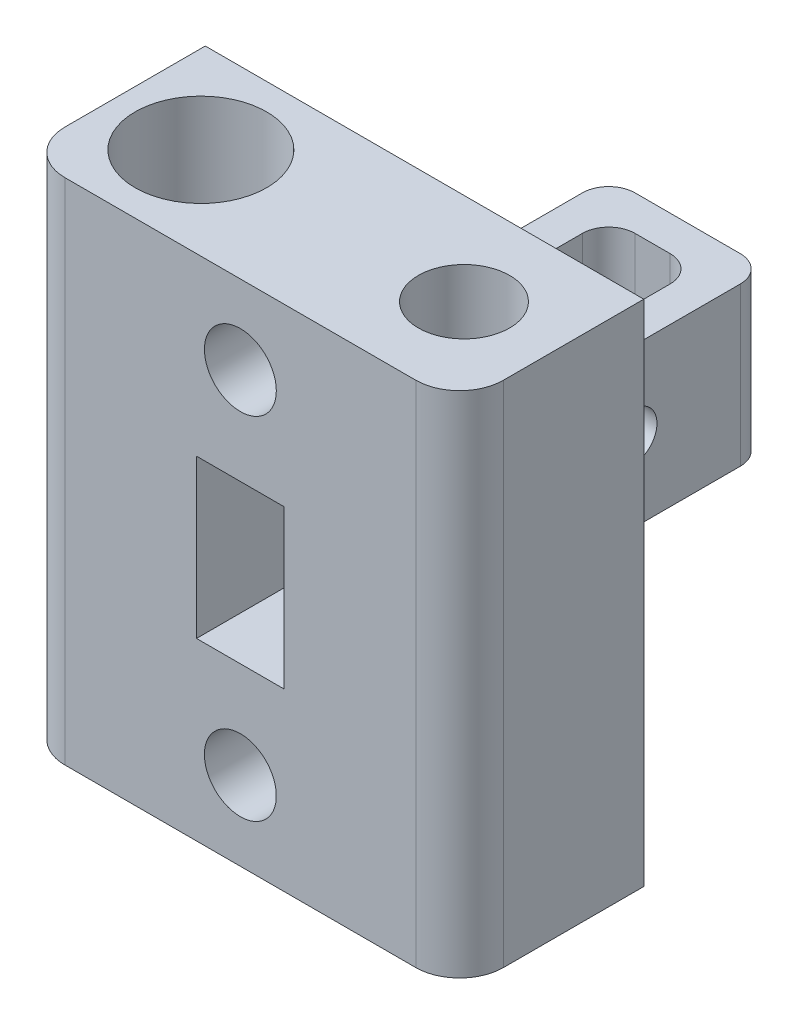
SolidWorks part; units mm, degrees
ref_plane "Front Plane" through (0, 0, 0) normal (0, 0, 1) x (1, 0, 0)
ref_plane "Top Plane" through (0, 0, 0) normal (0, 1, 0) x (1, 0, 0)
ref_plane "Right Plane" through (0, 0, 0) normal (1, 0, 0) x (0, 0, -1)
sketch "Sketch1" plane through (0, 0, 0) normal (0, 1, 0) x (1, 0, 0)
  line L1 (-25, 10.5) -> (25, 10.5)
  line L2 (-25, 10.5) -> (-25, -10.5)
  line L3 (-25, -10.5) -> (25, -10.5)
  line L4 (25, 10.5) -> (25, -10.5)
  line L5 (-25, 10.5) -> (25, -10.5) construction
  line L6 (-25, -10.5) -> (25, 10.5) construction
  point P0 (0, 0)
  dimension "D1" = 21
  dimension "D2" = 50
extrude "Boss-Extrude1" add sketch "Sketch1" along normal blind 58
sketch "Sketch3" plane through (0, 58, 0) normal (0, 1, 0) x (1, 0, 0)
  line L0 (-15, 0) -> (15, 0) construction
  circle A0 centre (-15, 0) radius 7.5
  dimension "D1" = 15
  dimension "D2" = 30
extrude "Cut-Extrude1" cut sketch "Sketch3" against normal blind 24 contours A0
sketch "Sketch4" plane through (0, 58, 0) normal (0, 1, 0) x (1, 0, 0)
  line L0 (-15, 0) -> (15, 0) construction
  circle A0 centre (15, 0) radius 5.2
  dimension "D1" = 10.4
extrude "Cut-Extrude2" cut sketch "Sketch4" against normal up to next
sketch "Sketch5" plane through (0, 0, 0) normal (0, -1, 0) x (1, 0, 0)
  circle A1 centre (-15, 0) radius 7.5
  circle A2 centre (-15, 0) radius 7.5
  dimension "D1" = 0
extrude "Cut-Extrude3" cut sketch "Sketch5" against normal blind 24
sketch "Sketch6" plane through (0, 0, 0) normal (0, -1, 0) x (1, 0, 0)
  circle A0 centre (-15, 0) radius 4.5
extrude "Cut-Extrude4" cut sketch "Sketch6" against normal up to next
sketch "Sketch7" plane through (0, 0, 10.5) normal (0, 0, 1) x (1, 0, 0)
  line L0 (0, 58) -> (0, 0) construction
  line L1 (-25, 58) -> (25, 58) construction
  line L2 (-25, 0) -> (25, 0) construction
  line L3 (-25, 29) -> (25, 29) construction
  line L4 (-25, 58) -> (-25, 0) construction
  line L5 (25, 58) -> (25, 0) construction
  circle A1 centre (0, 49) radius 4.1
  circle A2 centre (0, 9) radius 4.1
  point P24 (0, 9)
  dimension "D1" = 8.2
  dimension "D2" = 9
sketch "Sketch8" plane through (0, 0, 10.5) normal (0, 0, 1) x (1, 0, 0)
  line L0 (-25, 29) -> (25, 29) construction
  line L1 (-25, 58) -> (-25, 0) construction
  line L2 (25, 58) -> (25, 0) construction
  line L3 (0, 58) -> (0, 0) construction
  line L4 (-25, 58) -> (25, 58) construction
  line L6 (-5, 20) -> (5, 20)
  line L7 (-5, 20) -> (-5, 38)
  line L8 (-5, 38) -> (5, 38)
  line L9 (5, 20) -> (5, 38)
  line L10 (-5, 20) -> (5, 38) construction
  line L11 (-5, 38) -> (5, 20) construction
  point P11 (0, 29)
  dimension "D1" = 18
  dimension "D2" = 10
extrude "Cut-Extrude5" cut sketch "Sketch8" against normal up to next
sketch "Sketch10" plane through (0, 0, -10.5) normal (0, 0, -1) x (-1, 0, 0)
  line L0 (-25, 29) -> (25, 29) construction
  line L1 (-25, 58) -> (-25, 0) construction
  line L2 (25, 58) -> (25, 0) construction
  line L3 (0, 58) -> (0, 0) construction
  line L4 (-25, 58) -> (25, 58) construction
extrude "Cut-Extrude6" cut sketch "Sketch7" against normal blind 15
sketch "Sketch11" plane through (0, 0, -10.5) normal (0, 0, -1) x (-1, 0, 0)
  line L0 (-25, 29) -> (25, 29) construction
  line L1 (9, 38) -> (5, 38)
  line L2 (9, 38) -> (9, 20)
  line L3 (9, 20) -> (5, 20)
  line L4 (5, 38) -> (5, 20)
  line L5 (9, 38) -> (5, 20) construction
  line L6 (9, 20) -> (5, 38) construction
  line L7 (0, 58) -> (0, 0) construction
  line L8 (0, 58) -> (0, 0)
  line L9 (-9, 20) -> (-5, 20)
  line L10 (-5, 38) -> (-5, 20)
  line L11 (-9, 38) -> (-5, 38)
  line L12 (-9, 38) -> (-9, 20)
  point P0 (7, 29)
  line M7 (-5, 20) -> (-5, 38)
  line M9 (5, 38) -> (5, 20)
  dimension "D1" = 5
  dimension "D2" = 4
  dimension "D3" = 18
extrude "Boss-Extrude2" add sketch "Sketch11" along normal blind 26 contours L1 L4 L3 L2 M9 | L11 L12 L9 L10 M7 region at (-7, 29, -10.5) region at (7, 29, -10.5)
sketch "Sketch12" plane through (0, 0, -36.5) normal (0, 0, -1) x (-1, 0, 0)
  line L1 (9, 20) -> (-9, 20)
  line L2 (9, 20) -> (9, 38)
  line L3 (9, 38) -> (-9, 38)
  line L4 (-9, 20) -> (-9, 38)
extrude "Boss-Extrude3" add sketch "Sketch12" along normal blind 4
sketch "Sketch13" plane through (9, 0, 0) normal (1, 0, 0) x (0, 0, -1)
  line L3 (10.5, 29) -> (40.5, 29) construction
  line L4 (10.5, 38) -> (10.5, 20) construction
  line L5 (40.5, 38) -> (40.5, 20) construction
  line L6 (16.25, 29) -> (25.25, 29) construction
  line L7 (16.25, 31.75) -> (25.25, 31.75)
  line L8 (16.25, 26.25) -> (25.25, 26.25)
  arc A0 (16.25, 31.75) -> (16.25, 26.25) centre (16.25, 29) ccw
  arc A1 (25.25, 26.25) -> (25.25, 31.75) centre (25.25, 29) ccw
  point P1 (13.5, 29)
  point P14 (20.75, 29)
  dimension "D1" = 5.5
  dimension "D2" = 3
  dimension "D3" = 9
extrude "Cut-Extrude7" cut sketch "Sketch13" against normal through all
fillet "Fillet1" radius 5 2 edges at (-25, 29, 10.5) (25, 29, 10.5)
fillet "Fillet2" radius 5 4 edges at (-7, 20, -10.5) (7, 20, -10.5) (-7, 38, -10.5) (7, 38, -10.5)
fillet "Fillet3" radius 3 4 edges at (-5, 29, -36.5) (5, 29, -36.5) (-9, 29, -40.5) (9, 29, -40.5)
sketch "Sketch14" plane through (0, 0, 0) normal (0, -1, 0) x (1, 0, 0)
  line L0 (20.5508, 5.5508) -> (9.4492, -5.5508) construction
  line L1 (25, -10.5) -> (-25, -10.5) construction
  circle A0 centre (20.5508, 5.5508) radius 1.95
  circle A1 centre (15, 0) radius 5.2 construction
  circle A2 centre (9.4492, -5.5508) radius 1.95
  circle A3 centre (15, 0) radius 5.2 construction
  dimension "D1" = 7.85
  dimension "D2" = 3.9
  dimension "D3" = 3.9
  dimension "D4" = 7.85
  dimension "D5" = 45
extrude "Cut-Extrude8" cut sketch "Sketch14" against normal blind 10
